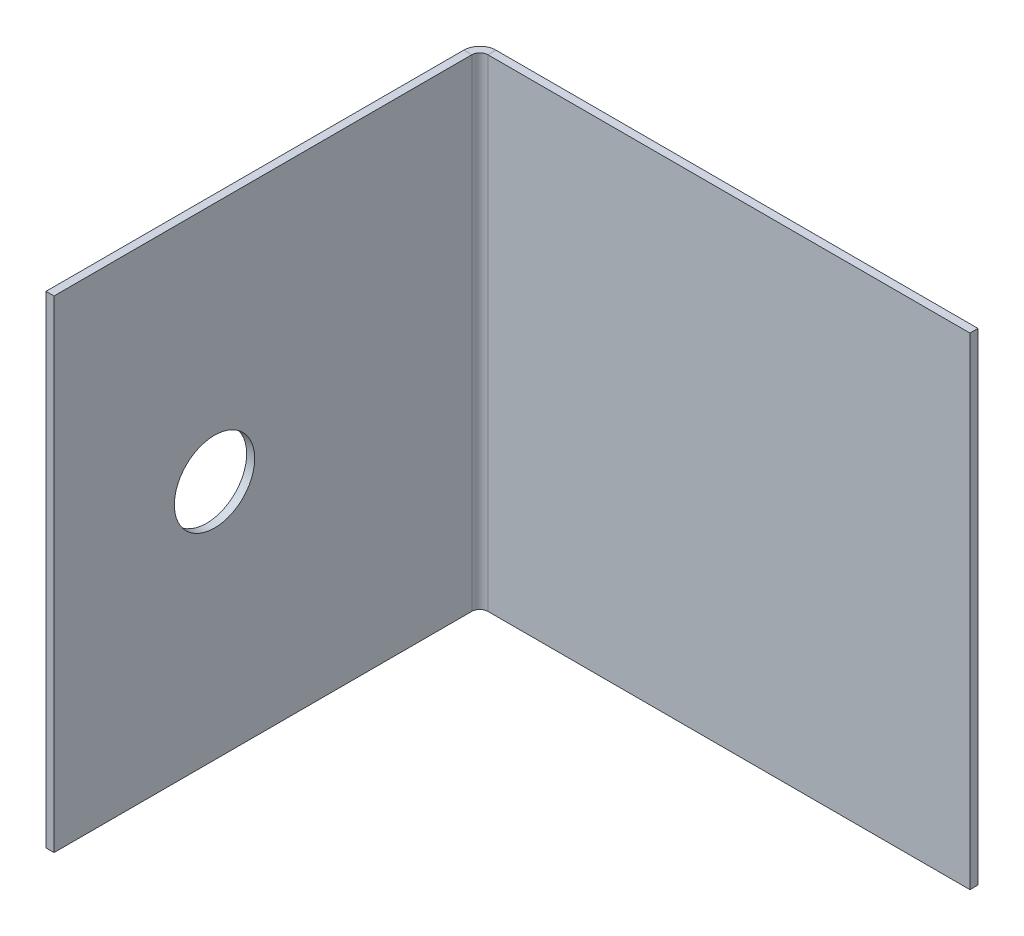
SolidWorks part; units mm, degrees
note: The reader was unsure of these and kept them because the rebuilt part matched: thickness of "基体-法兰1", "边线-法兰1", "钣金6", "钣金7", "钣金8"; flange length of "边线-法兰1".
ref_plane "前视基准面" through (0, 0, 0) normal (0, 0, 1) x (1, 0, 0)
ref_plane "上视基准面" through (0, 0, 0) normal (0, 1, 0) x (1, 0, 0)
ref_plane "右视基准面" through (0, 0, 0) normal (1, 0, 0) x (0, 0, -1)
sketch "草图1" plane through (0, 0, 0) normal (0, 0, 1) x (1, 0, 0)
  line L1 (-15, 15) -> (15, 15)
  line L2 (-15, 15) -> (-15, -15)
  line L3 (-15, -15) -> (15, -15)
  line L4 (15, 15) -> (15, -15)
  line L5 (-15, 15) -> (15, -15) construction
  line L6 (-15, -15) -> (15, 15) construction
  point P0 (0, 0)
  dimension "D1" = 30
  dimension "D2" = 30
base flange "基体-法兰1" sketch "草图1" thickness 0.5 reverse thickness direction no parameters "D1"=0.5
edge flange "边线-法兰1" sketch "草图9" flange angle 90 flange length 27 flange position bend outside bend radius 0.5 thickness 0.5 relief rectangular parameters "D1"=1, "D6"=10
sketch "草图9" plane through (-15, 0, 0) normal (-1, 0, 0) x (0, -1, 0)
  line L2 (-15, 0) -> (-15, 26.5)
  line L3 (-15, 26.5) -> (15, 26.5)
  line L4 (15, 26.5) -> (15, 0)
  line L7 (-15, 0) -> (15, 0) construction
  line L8 (-15, 0) -> (15, 0)
bend "边线折弯1" bend radius 0.5 bend angle 90 parameters "D5"=1
hole_wizard "M6 螺纹孔的螺纹孔钻头1" positions "3D草图1" profile "草图10" hole size "M6" standard "GB"
sketch3d "3D草图1"
  line L0 (-16, -15, 26.5) -> (-16, 15, 26.5) construction
  line L1 (-15.5, -15, 0.5) -> (-15.5, -15, 26.5) construction
  point P0 (-15.5, 0, 16.5125)
  dimension "D1" = 10
  dimension "D2" = 15
sketch "草图10" plane through (-15.5, 0, 16.5125) normal (0, 1, 0) x (0, 0, -1)
  line L0 (0, 0) -> (0, 16.5022)
  line L1 (0, 16.5022) -> (2.5, 15)
  line L2 (2.5, 15) -> (2.5, 0)
  line L5 (2.5, 0) -> (0, 0)
  line L10 (0, 16.5022) -> (-2.5, 15) construction
  line L11 (0, -6.35) -> (0, 107.95) construction
  dimension "孔直径" = 5
  dimension "孔深度" = 15
  dimension "导头角度" = 118
sketch "折弯-线1" plane through (0, 0, 0) normal (0, 1, 0) x (1, 0, 0)
sketch "边界框1" plane through (0, 0, 0) normal (0, 1, 0) x (1, 0, 0)
sheet metal parameters "钣金6" thickness 0.5 parameters "D1"=0.5
flat pattern "平板型式6" [suppressed]
sketch "折弯-线2" plane through (0, 0, 0) normal (0, 1, 0) x (1, 0, 0)
sketch "边界框2" [suppressed] plane through (0, 0, 0) normal (0, 1, 0) x (1, 0, 0)
sheet metal parameters "钣金7" thickness 0.5 parameters "D1"=0.5, "D7"=1
flat pattern "平板型式6" [suppressed]
sketch "折弯-线2" plane through (0, 0, 0) normal (0, 1, 0) x (1, 0, 0)
sketch "边界框2" [suppressed] plane through (0, 0, 0) normal (0, 1, 0) x (1, 0, 0)
bend of the flat pattern "展平-<边线折弯1>1"
sheet metal parameters "钣金8" thickness 0.5 parameters "D1"=0.5, "D7"=1
flat pattern "平板型式6" [suppressed]
sketch "折弯-线2" plane through (0, 0, 0) normal (0, 1, 0) x (1, 0, 0)
sketch "边界框2" [suppressed] plane through (0, 0, 0) normal (0, 1, 0) x (1, 0, 0)
bend of the flat pattern "展平-<边线折弯1>1"
